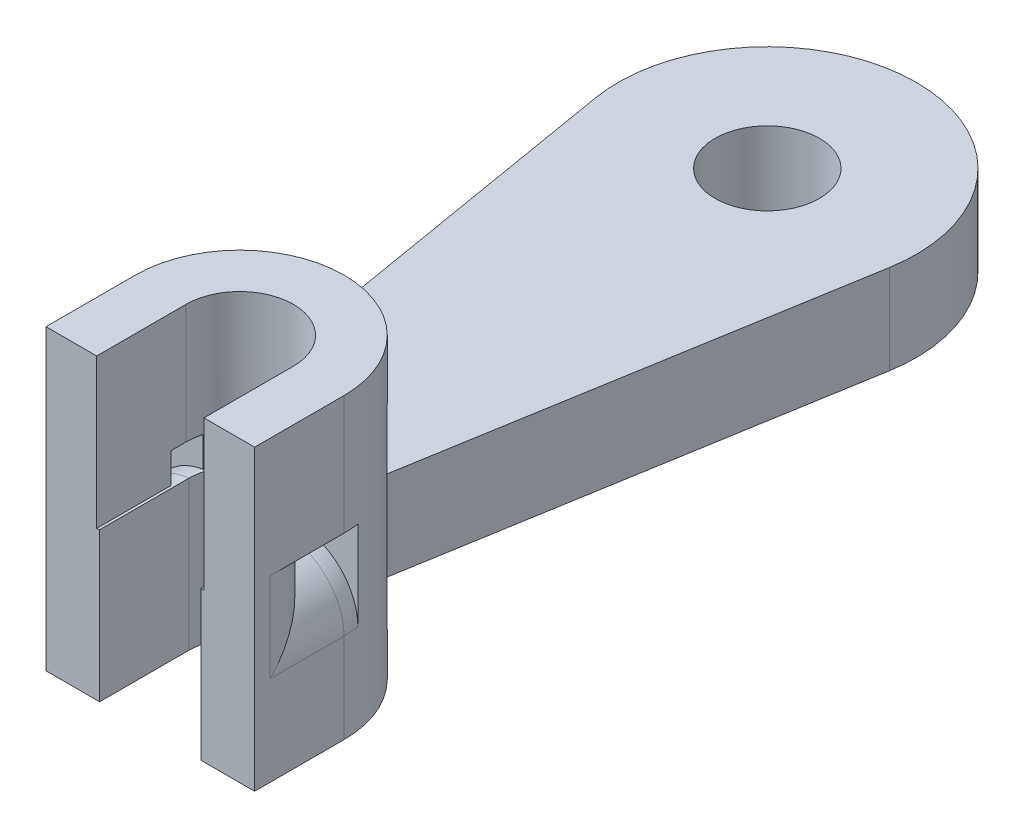
SolidWorks part; units mm, degrees
ref_plane "Front Plane" through (0, 0, 0) normal (0, 0, 1) x (1, 0, 0)
ref_plane "Top Plane" through (0, 0, 0) normal (0, 1, 0) x (1, 0, 0)
ref_plane "Right Plane" through (0, 0, 0) normal (1, 0, 0) x (0, 0, -1)
sketch "Sketch1" plane through (0, 0, 0) normal (0, 1, 0) x (1, 0, 0)
  line L0 (-1.7, 0) -> (-1.7, -3)
  line L1 (1.7, 0) -> (1.7, -3)
  line L2 (-3.5, 0) -> (-3.5, -3)
  line L3 (3.5, 0) -> (3.5, -3)
  line L4 (3.5, -3) -> (1.7, -3)
  line L5 (-1.7, -3) -> (-3.5, -3)
  arc A0 (1.7, 0) -> (-1.7, 0) centre (0, 0) ccw
  arc A1 (3.5, 0) -> (-3.5, 0) centre (0, 0) ccw
  dimension "D1" = 3.4
  dimension "D2" = 7
  dimension "D3" = 3
extrude "Boss-Extrude1" add sketch "Sketch1" along normal blind 5
sketch "Sketch2" plane through (0, 5, 0) normal (0, 1, 0) x (1, 0, 0)
  line L0 (-1.8, -2.9) -> (-1.8, 0)
  line L1 (1.8, 0) -> (1.8, -2.9)
  line L6 (1.7, 0) -> (1.7, -3)
  line L7 (1.7, -3) -> (3.5, -3)
  line L8 (3.5, -3) -> (3.5, 0)
  line L9 (-3.5, 0) -> (-3.5, -3)
  line L10 (-3.5, -3) -> (-1.7, -3)
  line L11 (-1.7, -3) -> (-1.7, 0)
  line L13 (1.8, -3) -> (3.5, -3)
  line L14 (3.5, -3) -> (3.5, 0)
  line L15 (-3.5, 0) -> (-3.5, -3)
  line L16 (-3.5, -3) -> (-1.8, -3)
  line L18 (-1.8, -2.9) -> (-1.8, -3)
  line L19 (1.8, -2.9) -> (1.8, -3)
  line L20 (1.7, -3) -> (3.5, -3) construction
  line L21 (-3.4, -2.9) -> (-1.8, -2.9) construction
  line L22 (-3.4, 0) -> (-3.4, -2.9) construction
  line L23 (1.8, -2.9) -> (3.4, -2.9) construction
  line L24 (3.4, -2.9) -> (3.4, 0) construction
  line L25 (1.7, 0) -> (1.7, -3) construction
  line L26 (-1.7, -3) -> (-1.7, 0) construction
  line L27 (-3.5, -3) -> (-1.7, -3) construction
  arc A0 (1.8, 0) -> (-1.8, 0) centre (0, 0) ccw
  arc A2 (1.7, 0) -> (-1.7, 0) centre (0, 0) ccw
  arc A3 (3.5, 0) -> (-3.5, 0) centre (0, 0) ccw
  arc A5 (3.5, 0) -> (-3.5, 0) centre (0, 0) ccw
  arc A6 (3.4, 0) -> (-3.4, 0) centre (0, 0) ccw construction
  arc A7 (1.7, 0) -> (-1.7, 0) centre (0, 0) ccw construction
  dimension "D1" = 0
  dimension "D2" = 0.1
extrude "Boss-Extrude2" add sketch "Sketch2" along normal blind 5
sketch "Sketch3" plane through (-1.8, 0, 0) normal (1, 0, 0) x (0, 0, -1)
  line L0 (-3, 5) -> (0, 5) construction
  line L1 (-0.5, 5) -> (0.5, 5)
  line L2 (-0.5, 5) -> (-0.5, 6)
  line L3 (-0.5, 6) -> (0.5, 6)
  line L4 (0.5, 5) -> (0.5, 6)
  line L5 (0, 10) -> (0, 5) construction
  point P6 (0, 5)
  dimension "D1" = 1
  dimension "D2" = 1
extrude "Cut-Extrude1" cut sketch "Sketch3" against normal through all both and the other way through all
fillet "Fillet1" radius 2 6 edges at (3.5, 5.5, 0.5) (-3.5, 5.5, 0.5) (3.5, 5, 0.25) (3.491, 5, -0.2506) (-3.491, 5, -0.2506) (-3.5, 5, 0.25)
sketch "Sketch4" plane through (0, 6, 0) normal (0, -1, 0) x (1, 0, 0)
  line L0 (0, -17.7) -> (0, 0) construction
  line L1 (-4.9305, -16.869) -> (-2.5, -2.4495)
  line L2 (2.5, -2.4495) -> (4.9305, -16.869)
  circle A0 centre (0, -17.7) radius 1.75
  arc A1 (-4.9305, -16.869) -> (4.9305, -16.869) centre (0, -17.7) ccw
  arc A2 (-2.5, -2.4495) -> (2.5, -2.4495) centre (0, 0) ccw
  arc A3 (-3.5, 0) -> (3.5, 0) centre (0, 0) ccw construction
  dimension "D1" = 3.5
  dimension "D3" = 10
  dimension "D2" = 17.7
  dimension "D4" = 5
extrude "Boss-Extrude3" add sketch "Sketch4" along normal blind 3
